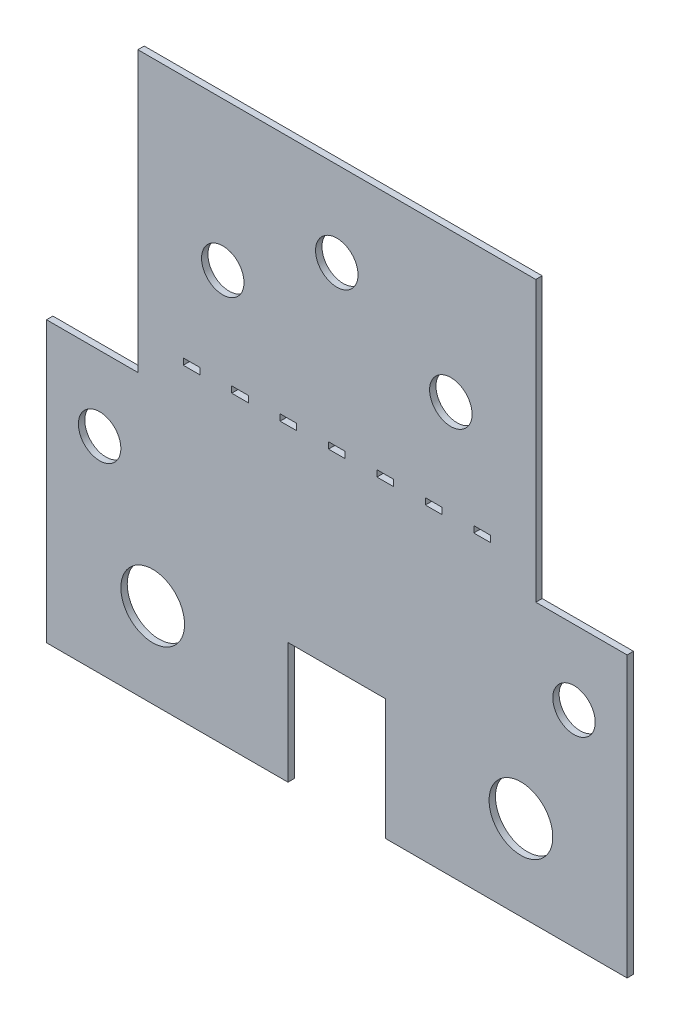
SolidWorks part; units mm, degrees
material "Oak"
ref_plane "Front Plane" through (0, 0, 0) normal (0, 0, 1) x (1, 0, 0)
ref_plane "Top Plane" through (0, 0, 0) normal (0, 1, 0) x (1, 0, 0)
ref_plane "Right Plane" through (0, 0, 0) normal (1, 0, 0) x (0, 0, -1)
sketch "Sketch1" plane through (0, 0, 0) normal (0, 0, 1) x (1, 0, 0)
  line L1 (0, 0) -> (273.4, 0)
  line L2 (0, 0) -> (0, -263.4)
  line L3 (0, -263.4) -> (273.4, -263.4)
  line L4 (273.4, 0) -> (273.4, -263.4)
  dimension "D1" = 273.4
  dimension "D2" = 263.4
extrude "Boss-Extrude1" add sketch "Sketch1" along normal blind 3
sketch "Sketch2" plane through (0, 0, 3) normal (0, 0, 1) x (1, 0, 0)
  line L1 (0, 0) -> (43, 0)
  line L2 (0, 0) -> (0, -131.64)
  line L3 (0, -131.64) -> (43, -131.64)
  line L4 (43, 0) -> (43, -131.64)
  line L9 (273.4, 0) -> (230.4, 0)
  line L10 (273.4, 0) -> (273.4, -131.64)
  line L11 (273.4, -131.64) -> (230.4, -131.64)
  line L12 (230.4, 0) -> (230.4, -131.64)
  dimension "D1" = 43
  dimension "D2" = 131.64
  dimension "D5" = 43
  dimension "D6" = 131.64
extrude "Cut-Extrude1" cut sketch "Sketch2" against normal through all
sketch "Sketch3" plane through (0, 0, 0) normal (0, 0, -1) x (-1, 0, 0)
  line L0 (0, -263.4) -> (-273.4, -263.4) construction
  line L1 (-159.7, -206.4) -> (-113.7, -206.4)
  line L2 (-159.7, -206.4) -> (-159.7, -263.4)
  line L3 (-159.7, -263.4) -> (-113.7, -263.4)
  line L4 (-113.7, -206.4) -> (-113.7, -263.4)
  line L5 (-273.4, -263.4) -> (-273.4, -131.64) construction
  dimension "D1" = 46
  dimension "D2" = 57
  dimension "D3" = 113.7
extrude "Cut-Extrude2" cut sketch "Sketch3" against normal through all
sketch "Sketch5" plane through (0, 0, 0) normal (0, 0, -1) x (-1, 0, 0)
  line L1 (-140.6, -115) -> (-132.8, -115)
  line L2 (-140.6, -115) -> (-140.6, -118)
  line L3 (-140.6, -118) -> (-132.8, -118)
  line L4 (-132.8, -115) -> (-132.8, -118)
  line L5 (-273.4, -263.4) -> (-273.4, -131.64) construction
  line L6 (-230.4, 0) -> (-43, 0) construction
  dimension "D1" = 7.8
  dimension "D2" = 3
  dimension "D3" = 132.8
  dimension "D4" = 115
extrude "Cut-Extrude3" cut sketch "Sketch5" against normal through all
pattern_linear "LPattern2" count 4 spacing 22.8 along (1, 0, 0) count 4 spacing 22.8 along (-1, 0, 0) of "Cut-Extrude3"
sketch "Sketch6" plane through (0, 0, 0) normal (0, 0, -1) x (-1, 0, 0)
  line L0 (-273.4, -263.4) -> (-273.4, -131.64) construction
  line L1 (-230.4, -131.64) -> (-273.4, -131.64) construction
  line L2 (0, -131.64) -> (-43, -131.64) construction
  line L3 (0, -131.64) -> (0, -263.4) construction
  line L4 (-159.7, -263.4) -> (-273.4, -263.4) construction
  line L5 (0, -263.4) -> (-113.7, -263.4) construction
  circle A0 centre (-248.4, -166.64) radius 10
  circle A1 centre (-25, -166.64) radius 10
  circle A2 centre (-223.4, -223.4) radius 15
  circle A3 centre (-50, -223.4) radius 15
  point P18 (0, 0)
  point P19 (0, 0)
  dimension "D3" = 20
  dimension "D6" = 20
  dimension "D9" = 30
  dimension "D10" = 30
  dimension "D1" = 25
  dimension "D2" = 35
  dimension "D4" = 35
  dimension "D5" = 25
  dimension "D7" = 50
  dimension "D8" = 40
  dimension "D11" = 40
  dimension "D12" = 50
extrude "Cut-Extrude4" cut sketch "Sketch6" against normal through all and the other way through all
sketch "Sketch8" plane through (0, 0, 0) normal (0, 0, -1) x (-1, 0, 0)
  line L0 (-230.4, 0) -> (-230.4, -131.64) construction
  line L1 (-43, -131.64) -> (-43, 0) construction
  line L2 (-230.4, 0) -> (-43, 0) construction
  circle A0 centre (-190.4, -70) radius 10
  circle A1 centre (-136.7, -40) radius 10
  circle A2 centre (-83, -70) radius 10
  point P12 (0, 0)
  dimension "D7" = 20
  dimension "D8" = 20
  dimension "D9" = 20
  dimension "D1" = 40
  dimension "D2" = 40
  dimension "D3" = 40
  dimension "D4" = 70
  dimension "D5" = 70
  dimension "D6" = 93.7
extrude "Cut-Extrude5" cut sketch "Sketch8" against normal through all
